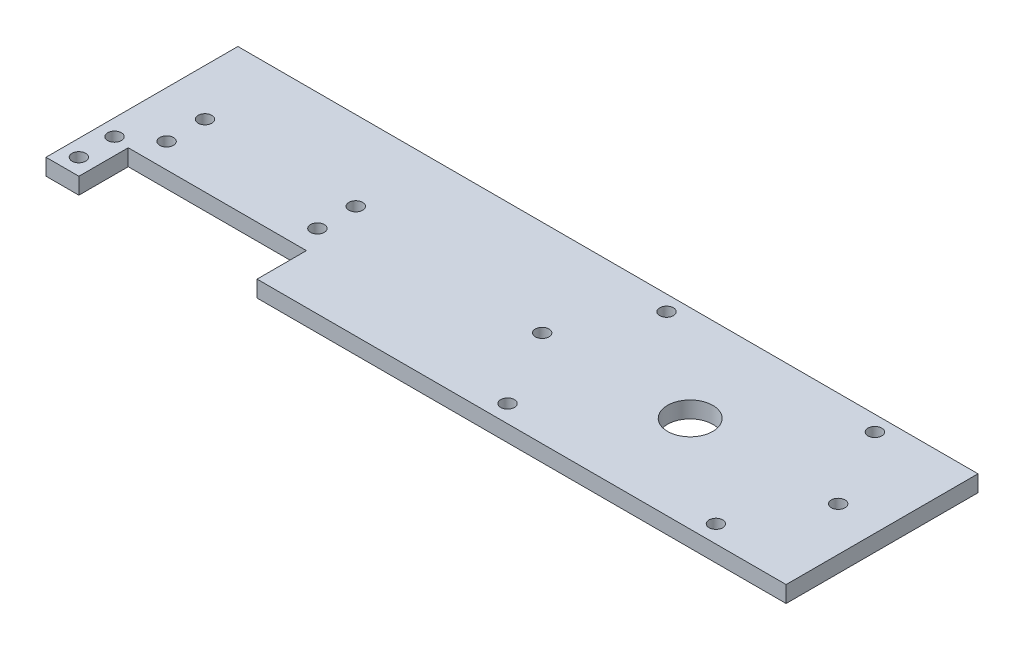
SolidWorks part; units mm, degrees
ref_plane "Front Plane" through (0, 0, 0) normal (0, 0, 1) x (1, 0, 0)
ref_plane "Top Plane" through (0, 0, 0) normal (0, 1, 0) x (1, 0, 0)
ref_plane "Right Plane" through (0, 0, 0) normal (1, 0, 0) x (0, 0, -1)
sketch "Sketch1" plane through (0, 0, 0) normal (0, 1, 0) x (1, 0, 0)
  line L0 (0, 13.2344) -> (0, -3.2344) construction
  line L1 (-100, 22.5) -> (35, 22.5)
  line L2 (-100, 22.5) -> (-100, -12.5)
  line L3 (-100, -12.5) -> (35, -12.5)
  line L4 (35, 22.5) -> (35, -12.5)
  line L5 (0, -1) -> (0, 11) construction
  line L6 (-35, -1) -> (35, -1)
  line L7 (-35, -1) -> (-35, 11)
  line L8 (-35, 11) -> (35, 11)
  line L9 (35, -1) -> (35, 11)
  line L10 (-35, -1) -> (35, 11) construction
  line L11 (-35, 11) -> (35, -1) construction
  circle A4 centre (0, 5) radius 4.125
  circle A5 centre (27, 5) radius 1.25
  circle A6 centre (-27, 5) radius 1.25
  circle A7 centre (-97, -9.5) radius 1.25
  circle A8 centre (-97, -3) radius 1.25
  circle A9 centre (-91.5, 8) radius 1.25
  circle A10 centre (-64, 8) radius 1.25
  circle A11 centre (-64, 1) radius 1.25
  circle A12 centre (-91.5, 1) radius 1.25
  point P0 (0, 0)
  point P25 (0, 0)
  dimension "D3" = 2.5
  dimension "D4" = 35
  dimension "D5" = 2.5
  dimension "D9" = 2.5
  dimension "D13" = 2.5
  dimension "D2" = 8.25
  dimension "D19" = 100
  dimension "D21" = 6
  dimension "D22" = 6
  dimension "D1" = 35
  dimension "D6" = 8
  dimension "D7" = 70
  dimension "D8" = 12
  dimension "D10" = 3
  dimension "D11" = 6.5
  dimension "D12" = 3
  dimension "D14" = 14.5
  dimension "D15" = 8.5
  dimension "D18" = 27.5
  dimension "D20" = 11.5
  dimension "D16" = 2
  dimension "D17" = 2
extrude "Boss-Extrude1" add sketch "Sketch1" along normal blind 3 contours L7 L8 L4 L1 L2 L3 L6 | L8 L7 L6 L4 A4 A5 A6 region at (-39.186, 0, -5.0312) region at (34.2898, 0, -5)
sketch "Sketch2" plane through (0, 0, 0) normal (0, 0, 1) x (1, 0, 0)
  line L0 (-94.5, 33) -> (-94.5, -17) construction
  line L1 (-92, 33) -> (-92, -17)
  line L2 (-97, 33) -> (-97, -17)
  line L3 (-89, 33) -> (-89, -17)
  line L4 (-100, 33) -> (-100, -17)
  line L5 (-100, 3) -> (-100, 0) construction
  line L7 (-94, 6.4998) -> (-61.5, 6.4998)
  line L8 (-94, 6.4998) -> (-94, -3.3981)
  line L9 (-94, -3.3981) -> (-61.5, -3.3981)
  line L10 (-61.5, 6.4998) -> (-61.5, -3.3981)
  arc A0 (-92, 33) -> (-97, 33) centre (-94.5, 33) ccw
  arc A1 (-97, -17) -> (-92, -17) centre (-94.5, -17) ccw
  arc A2 (-100, -17) -> (-89, -17) centre (-94.5, -17) ccw
  arc A3 (-89, 33) -> (-100, 33) centre (-94.5, 33) ccw
  point P2 (-94.5, 8)
  dimension "D4" = 5.5
  dimension "D1" = 3
  dimension "D2" = 3
  dimension "D3" = 5
  dimension "D5" = 50
  dimension "D6" = 50
  dimension "D7" = 6
  dimension "D8" = 32.5
extrude "Cut-Extrude3" cut sketch "Sketch2" along normal up to surface (12.5 mm away) from offset 3.5 contours L1 L9 L3 L7 | L10 L7 L3 L9 | L8 L9 L1 L7 region at (-90.5, 1.5509, 0) region at (-93, 1.5509, 0) region at (-75.25, 1.5509, 0) up to face at (-32.5, 1.5, 12.5)
ref_plane "Plane3" through (0, 3, 0) normal (0, -1, 0) x (-1, 0, 0)
sketch "Sketch3" plane through (0, 3, 0) normal (0, -1, 0) x (-1, 0, 0)
  line L0 (-35, -12.5) -> (27, -12.5)
  line L2 (27, 5) -> (27, -12.5) construction
  line L3 (-27, 5) -> (-27, -12.5) construction
  line L5 (-22.0043, 22.7064) -> (-22.0043, -12.2936)
  line L6 (-37.5, -12.5) -> (25.1934, -12.5) construction
  line L7 (27, -12.5) -> (27, 22.5)
  line L8 (100, 22.5) -> (-35, 22.5) construction
  line L9 (27, 22.5) -> (-35, 22.5)
  line L10 (22, 22.5) -> (22, -12.5)
  line L11 (-22.0043, 22.7064) -> (22, 22.5)
  line L12 (-22.0043, -12.2936) -> (22, -12.5)
  circle A4 centre (-19, -9.3076) radius 1.25
  circle A5 centre (19, -9.3076) radius 1.25
  circle A6 centre (19, 19.6924) radius 1.25
  circle A7 centre (-19, 19.6924) radius 1.25
  point P14 (-22.0043, 5.2064)
  dimension "D3" = 35
  dimension "D4" = 5
  dimension "D8" = 8
  dimension "D14" = 2.5
  dimension "D1" = 54
  dimension "D2" = 5
  dimension "D5" = 62
  dimension "D6" = 54
  dimension "D7" = 44.0043
  dimension "D9" = 3.0043
  dimension "D10" = 3
  dimension "D13" = 3
  dimension "D11" = 2
  dimension "D12" = 2
extrude "Cut-Extrude7" cut sketch "Sketch3" along normal blind 10 contours A4 | A7 | A6 | A5 region at (19, 3, 9.3076)
